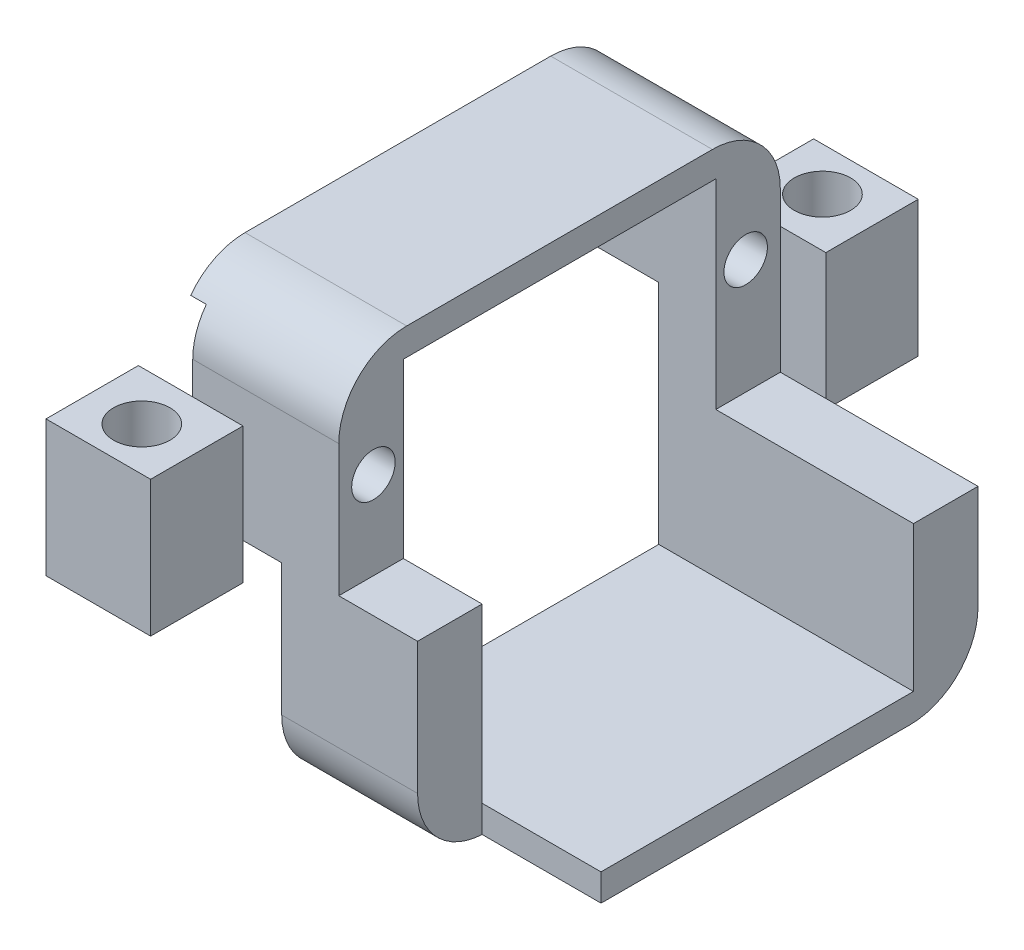
SolidWorks part; units mm, degrees
ref_plane "Front Plane" through (0, 0, 0) normal (0, 0, 1) x (1, 0, 0)
ref_plane "Top Plane" through (0, 0, 0) normal (0, 1, 0) x (1, 0, 0)
ref_plane "Right Plane" through (0, 0, 0) normal (1, 0, 0) x (0, 0, -1)
sketch "Sketch1" plane through (0, 0, 0) normal (0, 1, 0) x (1, 0, 0)
  line L0 (-1.1, 16.25) -> (-1.1, 11.5)
  line L1 (-17.65, -16.25) -> (17.65, -16.25)
  line L2 (-17.65, -16.25) -> (-17.65, 16.25)
  line L3 (-17.65, 16.25) -> (17.65, 16.25)
  line L4 (17.65, -16.25) -> (17.65, 16.25)
  line L5 (-17.65, -16.25) -> (17.65, 16.25) construction
  line L6 (-17.65, 16.25) -> (17.65, -16.25) construction
  line L7 (-1.1, 11.5) -> (17.65, 11.5)
  line L8 (-1.1, -16.25) -> (-1.1, -11.5)
  line L9 (-1.1, -11.5) -> (17.65, -11.5)
  line L10 (-1.1, 11.5) -> (-1.1, -11.5) construction
  line L11 (8.9, -11.5) -> (8.9, -16.25)
  line L12 (-8.8, 16.25) -> (-8.8, 11.5)
  line L13 (-8.8, 11.5) -> (-3.8, 11.5)
  line L14 (-3.8, 11.5) -> (-3.8, 16.25)
  line L15 (-3.8, -16.25) -> (-3.8, -11.5)
  line L16 (-3.8, -11.5) -> (-8.8, -11.5)
  line L17 (-8.8, -11.5) -> (-8.8, -16.25)
  line L18 (-8.8, 11.5) -> (-8.8, -11.5)
  line L19 (6.45, 16.25) -> (6.45, 23.05)
  line L20 (6.45, 23.05) -> (-1.25, 23.05)
  line L21 (-1.25, 23.05) -> (-1.25, 16.25)
  line L22 (-11.65, -16.25) -> (-11.65, -23.05)
  line L23 (-11.65, -23.05) -> (-3.95, -23.05)
  line L24 (-3.95, -23.05) -> (-3.95, -16.25)
  line L25 (9.53, -16.25) -> (9.53, -23.05)
  line L26 (9.53, -23.05) -> (17.23, -23.05)
  line L27 (17.23, -23.05) -> (17.23, -16.25)
  line L28 (-1.1, 11.5) -> (-1.1, -11.5)
  circle A0 centre (2.6, 19.85) radius 2.075
  circle A1 centre (13.38, -19.85) radius 2.075
  circle A2 centre (-7.8, -19.85) radius 2.075
  point P0 (0, 0)
  point P11 (-1.1, 0)
  point P31 (2.6, 23.05)
  point P45 (-7.8, -23.05)
  point P48 (13.38, -23.05)
  dimension "D11" = 4.15
  dimension "D18" = 4.15
  dimension "D19" = 4.15
  dimension "D1" = 32.5
  dimension "D2" = 23
  dimension "D3" = 8.75
  dimension "D4" = 10
  dimension "D5" = 16.55
  dimension "D6" = 2.7
  dimension "D7" = 5
  dimension "D8" = 20.25
  dimension "D9" = 7.7
  dimension "D10" = 6.8
  dimension "D12" = 9.85
  dimension "D13" = 31.03
  dimension "D14" = 7.7
  dimension "D15" = 19.85
  dimension "D16" = 7.7
  dimension "D17" = 6.8
  dimension "D20" = 19.85
extrude "Boss-Extrude1" add sketch "Sketch1" against normal blind 2 contours L7 L28 L9 L4 | L0 L7 L4 L3 | L11 L9 L8 L1 region at (8.275, 0, -13.875) region at (8.275, 0, 0) region at (3.9, 0, 13.875)
extrude "Boss-Extrude2" add sketch "Sketch1<3>" along normal blind 12.7 contours L0 L7 L4 L3 | L11 L9 L8 L1 region at (8.275, 0, -13.875) region at (3.9, 0, 13.875)
sketch "Sketch1<3>" plane through (0, 0, 0) normal (0, 1, 0) x (1, 0, 0) same geometry as "Sketch1"
sketch "Sketch3" plane through (0, 0, 0) normal (0, 1, 0) x (1, 0, 0)
  line L0 (3.1, 16.25) -> (3.1, 11.5)
  line L1 (-17.65, 16.25) -> (17.65, 16.25) construction
  line L2 (-1.1, 11.5) -> (17.65, 11.5) construction
  line L3 (3.1, 11.5) -> (-17.65, 11.5)
  line L4 (-17.65, -16.25) -> (-17.65, 16.25) construction
  line L5 (3.1, -16.25) -> (3.1, -11.5)
  line L6 (-17.65, -16.25) -> (17.65, -16.25) construction
  line L7 (-1.1, -11.5) -> (17.65, -11.5) construction
  line L8 (3.1, -11.5) -> (-17.65, -11.5)
  line L9 (3.1, 11.5) -> (3.1, -11.5)
  line L10 (-7.65, -11.5) -> (-7.65, -16.275)
  line L11 (3.1, 16.25) -> (-17.65, 16.25)
  line L12 (-17.65, 16.25) -> (-17.65, 11.5)
  line L13 (-17.65, -11.5) -> (-17.65, -16.25)
  line L14 (-17.65, -16.25) -> (3.1, -16.25)
  line L15 (-8.8, 11.5) -> (-8.8, -11.5)
  line L16 (-8.8, 11.5) -> (-8.8, 16.25)
  line L17 (-8.8, -11.5) -> (-8.8, -16.25)
  dimension "D1" = 20.75
  dimension "D2" = 10
extrude "Boss-Extrude3" add sketch "Sketch3" along normal blind 12.7 from surface contours L11 L12 L3 L0 | L10 L14 L5 L8 region at (-2.85, 0, -13.875) region at (-2.275, 0, 13.875) starting at face at (8.275, 12.7, -13.875)
extrude "Boss-Extrude4" add sketch "Sketch3<3>" along normal blind 2 from surface contours L16 L3 L0 L11 | L3 L15 L8 L9 | L10 L14 L5 L8 | L8 L17 L14 L10 region at (-2.85, 0, -13.875) region at (-2.85, 0, 0) region at (-2.275, 0, 13.875) region at (-8.225, 0, 13.875) starting at face at (-2.275, 25.4, 13.875)
sketch "Sketch3<3>" plane through (0, 0, 0) normal (0, 1, 0) x (1, 0, 0) same geometry as "Sketch3"
sketch "Sketch2" plane through (0, 0, 0) normal (1, 0, 0) x (0, 0, -1)
  line L0 (13.7, 6.45) -> (-13.7, 6.45) construction
  line L1 (-13.7, 19.15) -> (13.7, 19.15) construction
  circle A0 centre (13.7, 6.45) radius 1.6
  circle A1 centre (-13.7, 6.45) radius 1.6
  circle A2 centre (-13.7, 19.15) radius 1.6
  circle A3 centre (13.7, 19.15) radius 1.6
  point P4 (0, 6.45)
  dimension "D1" = 3.2
  dimension "D2" = 3.2
  dimension "D6" = 3.2
  dimension "D7" = 3.2
  dimension "D3" = 27.4
  dimension "D4" = 6.45
  dimension "D5" = 6.45
extrude "Cut-Extrude1" cut sketch "Sketch2" along normal blind 8 from surface contours A1 | A0 region at (0, 6.45, -13.7) region at (0, 6.45, 13.7) starting at face at (-1.1, 5.85, 0)
extrude "Cut-Extrude2" cut sketch "Sketch2<3>" against normal blind 8 from surface contours A3 | A2 region at (0, 19.15, 13.7) region at (0, 19.15, -13.7) starting at face at (3.1, 19.55, 0)
sketch "Sketch2<3>" plane through (0, 0, 0) normal (1, 0, 0) x (0, 0, -1) same geometry as "Sketch2"
extrude "Boss-Extrude5" add sketch "Sketch1<4>" along normal blind 10 from offset 10 contours L20 L21 L3 L19 A0 | L23 L24 L1 L22 A2 region at (-1.175, 0, -16.3527) region at (-4.0527, 0, 19.65)
sketch "Sketch1<4>" plane through (0, 0, 0) normal (0, 1, 0) x (1, 0, 0) same geometry as "Sketch1"
fillet "Fillet1" radius 5 4 edges at (3.9, -2, 16.25) (-2.85, 27.4, 16.25) (8.275, -2, -16.25) (-2.85, 27.4, -16.25)
sketch "Sketch5" plane through (0, 0, 0) normal (0, 1, 0) x (1, 0, 0)
  line L1 (17.65, 16.25) -> (3.1, 16.25)
  line L2 (17.65, 16.25) -> (17.65, 11.5)
  line L3 (17.65, 11.5) -> (3.1, 11.5)
  line L4 (3.1, 16.25) -> (3.1, 11.5)
extrude "Cut-Extrude3" cut sketch "Sketch5" against normal blind 2 from surface starting at face at (9.59, 12.7, -14.35)
sketch "Sketch6" plane through (0, 0, 0) normal (0, 1, 0) x (1, 0, 0)
  line L1 (-8.8, 11.5) -> (-1.1, 11.5)
  line L2 (-8.8, 11.5) -> (-8.8, 16.25)
  line L3 (-8.8, 16.25) -> (-1.1, 16.25)
  line L4 (-1.1, 11.5) -> (-1.1, 16.25)
extrude "Cut-Extrude4" cut sketch "Sketch6" along normal blind 4 from surface starting at face at (-4.21, 12.7, -14.35)
